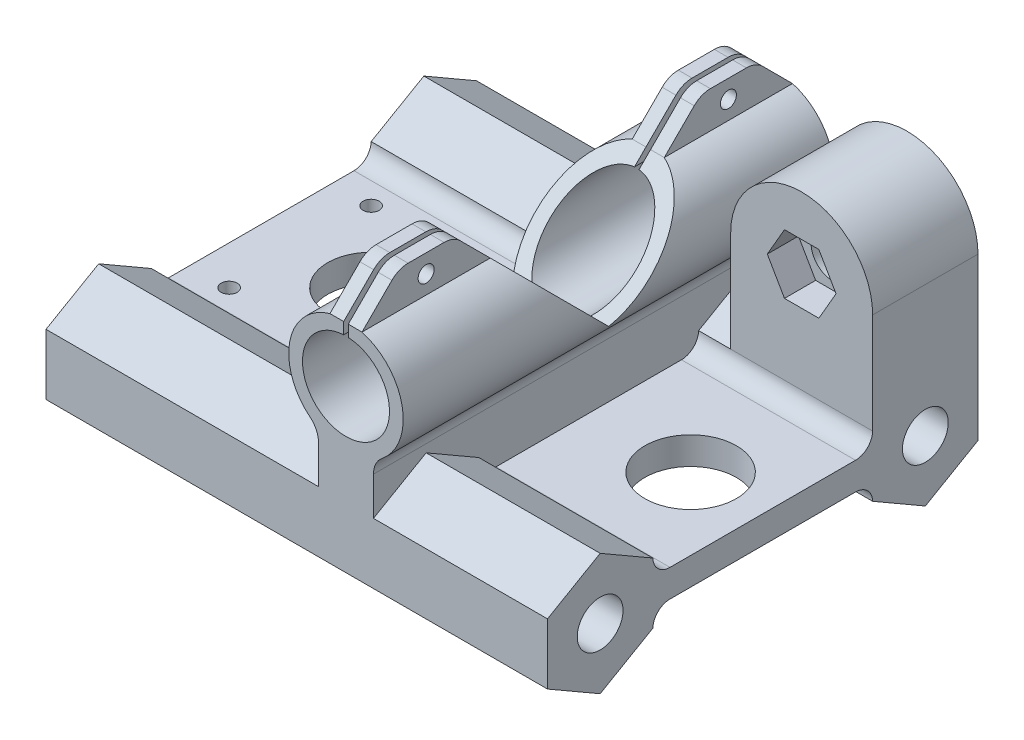
SolidWorks part; units mm, degrees
ref_plane "Front Plane" through (0, 0, 0) normal (0, 0, 1) x (1, 0, 0)
ref_plane "Top Plane" through (0, 0, 0) normal (0, 1, 0) x (1, 0, 0)
ref_plane "Right Plane" through (0, 0, 0) normal (1, 0, 0) x (0, 0, -1)
sketch "Sketch2" plane through (0, 0, 0) normal (1, 0, 0) x (0, 0, -1)
  line L0 (-12.6113, 0) -> (58.3887, 0) construction
  line L1 (-1.1113, 3) -> (46.8887, 3)
  line L2 (69.8887, 6.6395) -> (58.3887, 13.2791)
  line L3 (58.3887, 13.2791) -> (46.8887, 6.6395)
  line L4 (46.8887, 6.6395) -> (46.8887, 3)
  line L5 (46.8887, -6.6395) -> (58.3887, -13.2791)
  line L6 (58.3887, -13.2791) -> (69.8887, -6.6395)
  line L7 (69.8887, -6.6395) -> (69.8887, 6.6395)
  line L8 (-1.1113, 6.6395) -> (-12.6113, 13.2791)
  line L9 (-12.6113, 13.2791) -> (-24.1113, 6.6395)
  line L10 (-24.1113, 6.6395) -> (-24.1113, -6.6395)
  line L11 (-24.1113, -6.6395) -> (-12.6113, -13.2791)
  line L12 (-12.6113, -13.2791) -> (-1.1113, -6.6395)
  line L13 (-1.1113, -6.6395) -> (-1.1113, -3)
  line L14 (-1.1113, -3) -> (46.8887, -3)
  line L15 (46.8887, -3) -> (46.8887, -6.6395)
  line L16 (-1.1113, 3) -> (-1.1113, 6.6395)
  circle A2 centre (58.3887, 0) radius 11.5 construction
  circle A3 centre (-12.6113, 0) radius 11.5 construction
  dimension "D2" = 23
  dimension "D3" = 48
  dimension "D4" = 6
  dimension "D5" = 3
extrude "Boss-Extrude1" add sketch "Sketch2" along normal blind 109.5
sketch "Sketch3" plane through (0, 3, 0) normal (0, 1, 0) x (1, 0, 0)
  line L0 (0, 46.8887) -> (48, -1.1113) construction
  line L1 (109.5, -1.1113) -> (0, -1.1113) construction
  line L2 (0, -1.1113) -> (48, 46.8887) construction
  line L3 (109.5, 46.8887) -> (0, 46.8887) construction
  line L4 (109.5, -1.1113) -> (0, -1.1113) construction
  line L6 (39.5, 38.3887) -> (8.5, 38.3887) construction
  line L7 (39.5, 38.3887) -> (39.5, 7.3887) construction
  line L8 (39.5, 7.3887) -> (8.5, 7.3887) construction
  line L9 (8.5, 38.3887) -> (8.5, 7.3887) construction
  circle A0 centre (24, 22.8887) radius 9.5
  circle A1 centre (39.5, 38.3887) radius 1.75
  circle A2 centre (39.5, 7.3887) radius 1.75
  circle A3 centre (8.5, 7.3887) radius 1.75
  circle A4 centre (8.5, 38.3887) radius 1.75
  dimension "D4" = 3.5
  dimension "D5" = 19
  dimension "D1" = 45
  dimension "D2" = 45
  dimension "D3" = 31
extrude "Cut-Extrude1" cut sketch "Sketch3" against normal blind 28
fillet "Fillet3" radius 3.75 4 edges at (54.75, -3, 1.1113) (54.75, -3, -46.8887) (54.75, 3, -46.8887) (54.75, 3, 1.1113)
sketch "Sketch4" plane through (0, 0, -69.8887) normal (0, 0, -1) x (-1, 0, 0)
  line L0 (-65.5, 3) -> (-65.5, 28.6118) construction
  line L1 (-109.5, 3) -> (0, 3) construction
  line L2 (-41.25, 3) -> (-41.25, -3) construction
  line L3 (-71.5, 3) -> (-71.5, 17.6459)
  line L4 (-59.5, 3) -> (-59.5, 17.6459)
  line L5 (-59.5, 3) -> (-71.5, 3)
  line L6 (-62, 40.6118) -> (-62, 48.6118)
  line L7 (-62, 48.6118) -> (-65, 48.6118)
  line L8 (-65, 48.6118) -> (-65, 41.1018)
  line L9 (-69, 48.6118) -> (-66, 48.6118)
  line L10 (-66, 48.6118) -> (-66, 41.1018)
  line L11 (-69, 40.6118) -> (-69, 48.6118)
  line L12 (-66, 41.1018) -> (-66, 38.0986)
  line L13 (-65, 41.1018) -> (-65, 38.0986)
  arc A0 (-66, 38.0986) -> (-65, 38.0986) centre (-65.5, 28.6118) ccw
  arc A1 (-59.5, 17.6459) -> (-62, 40.6118) centre (-65.5, 28.6118) ccw
  arc A3 (-69, 40.6118) -> (-71.5, 17.6459) centre (-65.5, 28.6118) ccw
  dimension "D1" = 19
  dimension "D2" = 25
  dimension "D3" = 24.25
  dimension "D4" = 12
  dimension "D5" = 6
  dimension "D6" = 3
  dimension "D7" = 0.5
  dimension "D8" = 8
extrude "Boss-Extrude2" add sketch "Sketch4" against normal up to surface (94 mm away) up to face at (54.75, 0, 24.1113)
fillet "Fillet4" radius 5 2 edges at (59.5, 17.6459, -22.8887) (71.5, 17.6459, -22.8887)
sketch "Sketch5" plane through (0, 0, -69.8887) normal (0, 0, -1) x (-1, 0, 0)
  line L0 (-65.5, 28.6118) -> (-110, 28.6118) construction
  line L1 (-109.5, 28.6118) -> (-109.5, 6.6395)
  line L2 (-109.5, 6.6395) -> (-71.5, 6.6395) construction
  line L3 (-109.5, 6.6395) -> (-78.5, 6.6395)
  line L4 (-78.5, 6.6395) -> (-78.5, 28.6118)
  circle A0 centre (-94, 28.6118) radius 4.75
  arc A1 (-78.5, 28.6118) -> (-109.5, 28.6118) centre (-94, 28.6118) ccw
  dimension "D1" = 9.5
  dimension "D3" = 31
  dimension "D2" = 28.5
extrude "Boss-Extrude7" add sketch "Sketch5" against normal blind 23
sketch "Sketch6" plane through (0, 0, -46.8887) normal (0, 0, 1) x (1, 0, 0)
  line L1 (101.5056, 28.6118) -> (97.7528, 35.1118)
  line L2 (97.7528, 35.1118) -> (90.2472, 35.1118)
  line L3 (90.2472, 35.1118) -> (86.4944, 28.6118)
  line L4 (86.4944, 28.6118) -> (90.2472, 22.1118)
  line L5 (90.2472, 22.1118) -> (97.7528, 22.1118)
  line L6 (97.7528, 22.1118) -> (101.5056, 28.6118)
  circle A0 centre (94, 28.6118) radius 6.5 construction
  dimension "D1" = 13
extrude "Cut-Extrude2" cut sketch "Sketch6" against normal blind 6.8
sketch "Sketch7" plane through (0, 0, 0) normal (-1, 0, 0) x (0, 0, 1)
  line L0 (-69.8887, 18.8899) -> (24.1113, 18.8899) construction
  line L1 (-69.8887, 40.6118) -> (-41.8887, 40.6118) construction
  line L2 (-69.8887, 40.6118) -> (-69.8887, 18.8899) construction
  line L3 (-69.8887, 18.8899) -> (-41.8887, 18.8899) construction
  line L4 (-41.8887, 40.6118) -> (-41.8887, 18.8899) construction
  line L5 (24.1113, 40.6118) -> (-69.8887, 40.6118) construction
  line L6 (24.1113, 18.8899) -> (-3.8887, 18.8899) construction
  line L7 (24.1113, 18.8899) -> (24.1113, 40.6118) construction
  line L8 (24.1113, 40.6118) -> (-3.8887, 40.6118) construction
  line L9 (-3.8887, 18.8899) -> (-3.8887, 40.6118) construction
  line L10 (24.1113, 44.6118) -> (-69.8887, 44.6118) construction
  line L11 (24.1113, 48.6118) -> (24.1113, 40.6118) construction
  line L12 (-69.8887, 40.6118) -> (-69.8887, 48.6118) construction
  line L13 (-55.8887, 40.6118) -> (-55.8887, 48.6118) construction
  line L14 (24.1113, 48.6118) -> (-69.8887, 48.6118) construction
  line L15 (10.1113, 40.6118) -> (10.1113, 48.6118) construction
  line L16 (-41.8887, 40.6118) -> (-22.8887, 21.6118)
  line L17 (-3.8887, 40.6118) -> (-22.8887, 21.6118)
  line L18 (-3.8887, 40.6118) -> (-3.8887, 48.6118)
  line L19 (-41.8887, 40.6118) -> (-41.8887, 48.6118)
  line L20 (-41.8887, 48.6118) -> (-3.8887, 48.6118)
  circle A0 centre (10.1113, 44.6118) radius 1.75
  circle A1 centre (-55.8887, 44.6118) radius 1.75
  dimension "D3" = 3.5
  dimension "D1" = 28
  dimension "D2" = 28
extrude "Cut-Extrude3" cut sketch "Sketch7" against normal up to surface (78.5 mm away) up to face at (78.5, 16.7563, -58.3887)
chamfer "Chamfer1" distance 8 angle 45 8 edges at (67.5, 48.6118, -69.8887) (63.5, 48.6118, -69.8887) (67.5, 48.6118, -3.8887) (63.5, 48.6118, -3.8887) (63.5, 48.6118, -41.8887) (67.5, 48.6118, -41.8887) (67.5, 48.6118, 24.1113) (63.5, 48.6118, 24.1113)
fillet "Fillet5" radius 5 8 edges at (63.5, 48.6118, -61.8887) (67.5, 48.6118, -61.8887) (67.5, 48.6118, -49.8887) (63.5, 48.6118, -49.8887) (67.5, 48.6118, 4.1113) (63.5, 48.6118, 4.1113) (67.5, 48.6118, 16.1113) (63.5, 48.6118, 16.1113)
sketch "Sketch8" plane through (0, -3, 0) normal (0, -1, 0) x (1, 0, 0)
  line L0 (109.5, -22.8887) -> (24, -22.8887) construction
  line L1 (109.5, -2.6371) -> (109.5, -43.1404) construction
  line L2 (93.5, -2.6371) -> (93.5, -43.1404) construction
  line L3 (109.5, -2.6371) -> (0, -2.6371) construction
  line L4 (0, -43.1404) -> (109.5, -43.1404) construction
  circle A0 centre (93.75, -22.8887) radius 10
  dimension "D2" = 20
  dimension "D1" = 16
extrude "Cut-Extrude4" cut sketch "Sketch8" against normal blind 6.8
sketch "Sketch9" plane through (109.5, 0, 0) normal (1, 0, 0) x (0, 0, -1)
  line L0 (-18.3613, 9.9593) -> (-6.8613, -9.9593) construction
  line L1 (-12.6113, 13.2791) -> (-24.1113, 6.6395) construction
  line L2 (-12.6113, -13.2791) -> (-1.1113, -6.6395) construction
  line L3 (52.6387, -9.9593) -> (64.1387, 9.9593) construction
  line L4 (46.8887, -6.6395) -> (58.3887, -13.2791) construction
  circle A0 centre (58.3887, 0) radius 5
  circle A1 centre (-12.6113, 0) radius 5
  dimension "D1" = 10
extrude "Cut-Extrude5" cut sketch "Sketch9" against normal up to surface (50 mm away) up to face at (59.5, 8.7598, -22.8887)
